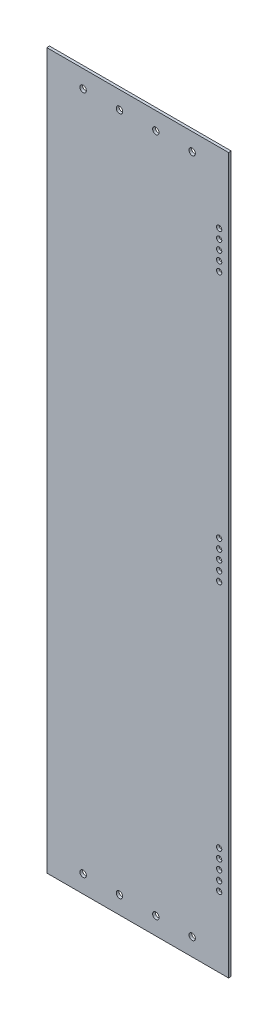
SolidWorks part; units mm, degrees
material "5052-H32"
ref_plane "Front Plane" through (0, 0, 0) normal (0, 0, 1) x (1, 0, 0)
ref_plane "Top Plane" through (0, 0, 0) normal (0, 1, 0) x (1, 0, 0)
ref_plane "Right Plane" through (0, 0, 0) normal (1, 0, 0) x (0, 0, -1)
sketch "Sketch1" plane through (0, 0, 0) normal (0, 0, 1) x (1, 0, 0)
  line L0 (55, 0) -> (-55, 0) construction
  line L1 (-77.5, 304.8) -> (77.5, 304.8)
  line L2 (-77.5, 304.8) -> (-77.5, -304.8)
  line L3 (-77.5, -304.8) -> (77.5, -304.8)
  line L4 (77.5, 304.8) -> (77.5, -304.8)
  line L5 (-77.5, 304.8) -> (77.5, -304.8) construction
  line L6 (-77.5, -304.8) -> (77.5, 304.8) construction
  point P0 (0, 0)
  point P5 (69.5, 244.8)
  point P7 (69.5, 228.8)
  point P8 (69.5, 236.8)
  point P9 (69.5, 220.8)
  point P10 (69.5, 212.8)
  point P11 (69.5, 8)
  point P12 (69.5, 16)
  point P13 (69.5, -212.8)
  point P14 (69.5, -228.8)
  point P15 (69.5, -220.8)
  point P16 (69.5, -236.8)
  point P17 (69.5, -244.8)
  point P18 (69.5, -8)
  point P19 (69.5, -16)
  point P20 (-46.5, 289.795)
  point P21 (-15.5, 289.795)
  point P22 (69.5, 0)
  point P23 (15.5, 289.795)
  point P24 (46.5, 289.795)
  point P25 (0, 0)
  point P26 (0, 0)
  point P29 (46.5, -289.795)
  point P30 (15.5, -289.795)
  point P31 (-15.5, -289.795)
  point P32 (-46.5, -289.795)
  dimension "D1" = 609.6
  dimension "D2" = 155
  dimension "D3" = 8
  dimension "D4" = 60
  dimension "D5" = 8
  dimension "D6" = 8
  dimension "D7" = 8
  dimension "D8" = 8
  dimension "D9" = 60
  dimension "D10" = 8
  dimension "D11" = 8
  dimension "D12" = 8
  dimension "D13" = 8
  dimension "D14" = 8
  dimension "D15" = 8
  dimension "D16" = 8
  dimension "D17" = 8
  dimension "D18" = 8
  dimension "D19" = 8
  dimension "D20" = 31
  dimension "D21" = 31
  dimension "D22" = 31
  dimension "D23" = 31
  dimension "D24" = 15.005
extrude "Boss-Extrude1" add sketch "Sketch1" along normal blind 2.305
hole_wizard "M4 Clearance Hole1" positions "Sketch3" profile "Sketch5" hole size "M4" standard "ANSI Metric" end condition through all
sketch "Sketch3" plane through (0, 0, 2.305) normal (0, 0, 1) x (1, 0, 0)
  point P4 (69.5, 228.8)
  point P9 (69.5, 244.8)
  point P12 (69.5, 236.8)
  point P15 (69.5, 220.8)
  point P18 (69.5, 212.8)
  point P21 (69.5, 16)
  point P24 (69.5, 8)
  point P27 (69.5, 0)
  point P30 (69.5, -8)
  point P33 (69.5, -16)
  point P36 (69.5, -212.8)
  point P39 (69.5, -220.8)
  point P42 (69.5, -228.8)
  point P45 (69.5, -236.8)
  point P48 (69.5, -244.8)
sketch "Sketch5" plane through (69.5, 228.8, 2.305) normal (1, 0, 0) x (0, -1, 0)
  line L0 (0, 0) -> (0, 2.305)
  line L1 (0, 2.305) -> (2.25, 2.305)
  line L2 (2.25, 2.305) -> (2.25, 0)
  line L5 (2.25, 0) -> (0, 0)
  line L11 (0, -6.35) -> (0, 107.95) construction
  dimension "Thru Hole Dia." = 4.5
  dimension "Thru Hole Depth" = 2.305
hole_wizard "M5 Clearance Hole1" positions "Sketch6" profile "Sketch7" hole size "M5" standard "ANSI Metric" end condition through all
sketch "Sketch6" plane through (0, 0, 2.305) normal (0, 0, 1) x (1, 0, 0)
  point P0 (-46.5, -289.795)
  point P3 (-15.5, -289.795)
  point P6 (15.5, -289.795)
  point P9 (46.5, -289.795)
  point P12 (-46.5, 289.795)
  point P15 (-15.5, 289.795)
  point P18 (15.5, 289.795)
  point P21 (46.5, 289.795)
sketch "Sketch7" plane through (-46.5, -289.795, 2.305) normal (1, 0, 0) x (0, -1, 0)
  line L0 (0, 0) -> (0, 2.305)
  line L1 (0, 2.305) -> (2.75, 2.305)
  line L2 (2.75, 2.305) -> (2.75, 0)
  line L5 (2.75, 0) -> (0, 0)
  line L11 (0, -6.35) -> (0, 107.95) construction
  dimension "Thru Hole Dia." = 5.5
  dimension "Thru Hole Depth" = 2.305
